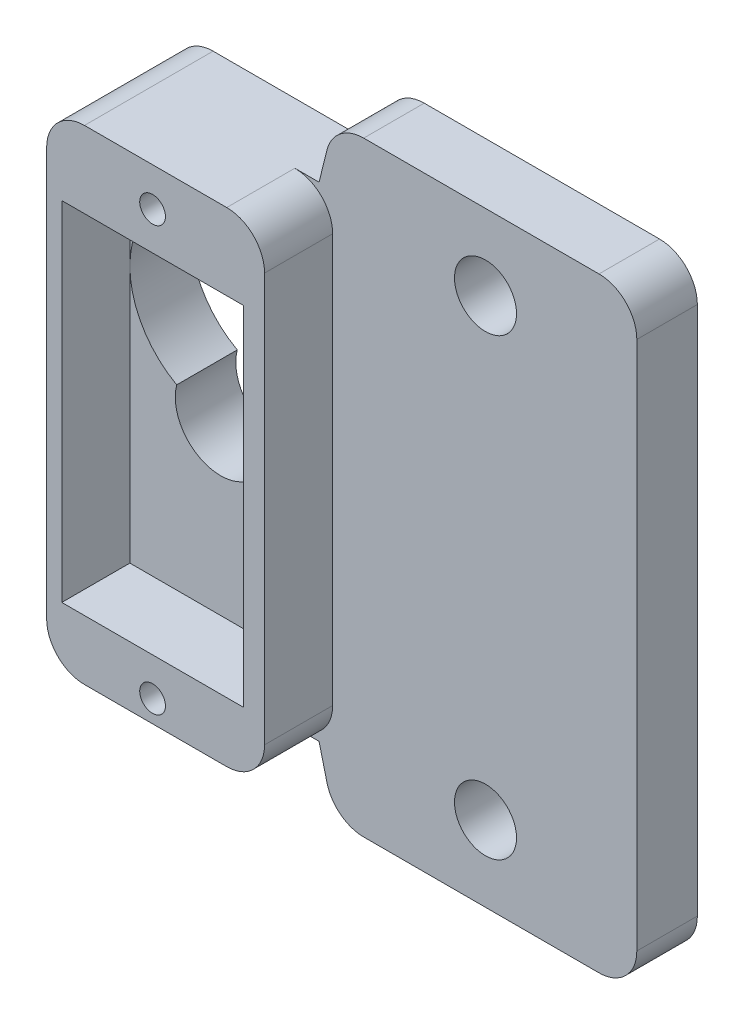
SolidWorks part; units mm, degrees
ref_plane "Plan de face" through (0, 0, 0) normal (0, 0, 1) x (1, 0, 0)
ref_plane "Plan de dessus" through (0, 0, 0) normal (0, 1, 0) x (1, 0, 0)
ref_plane "Plan de droite" through (0, 0, 0) normal (1, 0, 0) x (0, 0, -1)
sketch "Esquisse1" plane through (0, 0, 0) normal (0, 0, 1) x (1, 0, 0)
  line L0 (0, 19.6765) -> (0, -23.203) construction
  line L1 (-40.2718, 0) -> (44.7659, 0) construction
  line L2 (0, 20) -> (20, 20)
  line L3 (20, 20) -> (20, -20)
  line L4 (20, -20) -> (0, -20)
  line L5 (0, -20) -> (-14.5, -20) construction
  line L6 (-14.5, -20) -> (-14.5, 20) construction
  line L7 (-14.5, 20) -> (0, 20) construction
  line L8 (-7.5, 20) -> (-7.5, -20) construction
  line L9 (10, 20) -> (10, -20) construction
  line L10 (0, 20) -> (0, 16) construction
  line L11 (0, 16) -> (-14.5, 16) construction
  line L12 (-14.5, 16) -> (-14.5, -16)
  line L13 (0, -20) -> (0, -16) construction
  line L14 (0, -16) -> (-14.5, -16) construction
  line L15 (0, 20) -> (-1, 16)
  line L16 (-1, 16) -> (-14.5, 16)
  line L17 (-1, -16) -> (-14.5, -16)
  line L18 (0, -20) -> (-1, -16)
  circle A0 centre (-7.5, 4.95) radius 6 construction
  circle A1 centre (10, 15) radius 2.05
  circle A2 centre (10, -15) radius 2.05
  arc A3 (-10.4047, -0.3) -> (-4.5953, -0.3) centre (-7.5, -1.05) ccw construction
  arc A4 (-10.4047, -0.3) -> (-4.5953, -0.3) centre (-7.5, 4.95) cw
  arc A5 (-10.4047, -0.3) -> (-4.5953, -0.3) centre (-7.5, -1.05) ccw
  point P30 (-14.5, 0)
  dimension "D4" = 12
  dimension "D5" = 3
  dimension "D7" = 7
  dimension "D9" = 4.1
  dimension "D1" = 20
  dimension "D2" = 40
  dimension "D3" = 7.5
  dimension "D6" = 4.95
  dimension "D8" = 15
  dimension "D10" = 16
  dimension "D11" = 1
extrude "Boss.-Extru.1" add sketch "Esquisse1" along normal blind 4 contours L7 L6 L5 L4 L3 L2 A5 A4 A1 A2 region at (4.7951, -0.4724, 0)
sketch "Esquisse2" plane through (0, 0, 4) normal (0, 0, 1) x (1, 0, 0)
  line L0 (-7.5, 16.6119) -> (-7.5, -16.6119) construction
  line L1 (-0.1, 13.5) -> (-0.1, -13.5)
  line L2 (-1.5, -12.05) -> (-13.5, -12.05)
  line L3 (-1.5, -12.05) -> (-1.5, 10.95)
  line L4 (20, 20) -> (0, 20)
  line L5 (-1, -16) -> (0, -20)
  line L6 (0, -20) -> (20, -20)
  line L7 (20, -20) -> (20, 20)
  line L8 (20, 20) -> (0, 20)
  line L10 (0, -20) -> (20, -20)
  line L11 (20, -20) -> (20, 20)
  line L12 (-1.5, 10.95) -> (-13.5, 10.95)
  line L13 (-13.5, -12.05) -> (-13.5, 10.95)
  line L14 (-1.5, -12.05) -> (-13.5, 10.95) construction
  line L15 (-1.5, 10.95) -> (-13.5, -12.05) construction
  line L21 (-0.1, -16) -> (-1, -16)
  line L23 (-2.6, 16) -> (-14.5, 16)
  line L24 (-14.5, -16) -> (-2.6, -16)
  line L28 (-1, -16) -> (0, -20)
  line L30 (0, 20) -> (-1, 16)
  line L32 (0, 20) -> (-1, 16)
  line L34 (-1, 16) -> (-14.5, 16)
  line L36 (-14.5, 16) -> (-14.5, -16)
  line L37 (-14.5, 16) -> (-14.5, -16)
  line L38 (-1, 16) -> (-14.5, 16)
  line L39 (-14.5, -16) -> (-1, -16)
  line L40 (-14.5, -16) -> (-1, -16)
  arc A0 (-10.4047, -0.3) -> (-4.5953, -0.3) centre (-7.5, -1.05) ccw construction
  arc A1 (-4.5953, -0.3) -> (-10.4047, -0.3) centre (-7.5, 4.95) ccw construction
  arc A2 (-10.4047, -0.3) -> (-4.5953, -0.3) centre (-7.5, -1.05) ccw
  arc A3 (-4.5953, -0.3) -> (-10.4047, -0.3) centre (-7.5, 4.95) ccw
  arc A4 (-0.1, -13.5) -> (-2.6, -16) centre (-2.6, -13.5) cw
  arc A5 (-0.1, 13.5) -> (-2.6, 16) centre (-2.6, 13.5) ccw
  point P10 (-7.5, -0.55)
  point P15 (-7.5, -0.55)
  dimension "D4" = 2.5
  dimension "D5" = 2.5
  dimension "D2" = 23
  dimension "D3" = 1.4
  dimension "D1" = 0
extrude "Boss.-Extru.2" add sketch "Esquisse2" along normal blind 4.5 contours L2 L13 L12 L3 region at (-0.4509, 0, 4)
sketch "Esquisse3" plane through (0, 0, 8.5) normal (0, 0, 1) x (1, 0, 0)
  line L0 (-7.5, 37.9) -> (-7.5, -16) construction
  line L1 (-1.5, 10.95) -> (-7.5, 10.95) construction
  line L2 (-1.5, -12.05) -> (-13.5, -12.05) construction
  line L4 (-0.1, -13.5) -> (-0.1, 13.5)
  line L5 (-2.6, 16) -> (-14.5, 16)
  line L12 (-7.5, 10.95) -> (-13.5, 10.95) construction
  line L13 (-1.5, -12.05) -> (-13.5, -12.05) construction
  line L14 (-7.5, 10.95) -> (-13.5, 10.95)
  line L16 (-14.5, 16) -> (-14.5, -16)
  line L18 (-14.5, 16) -> (-14.5, -16)
  line L19 (-2.6, 16) -> (-14.5, 16)
  line L21 (-14.5, -16) -> (-2.6, -16)
  line L22 (-14.5, -16) -> (-2.6, -16)
  line L24 (-1.5, -12.05) -> (-13.5, -12.05)
  line L25 (-1.5, 10.95) -> (-7.5, 10.95)
  line L34 (-0.1, -13.5) -> (-0.1, 13.5)
  circle A0 centre (-7.5, 13.45) radius 0.85
  circle A1 centre (-7.5, -14.55) radius 0.85
  arc A2 (-0.1, -13.5) -> (-2.6, -16) centre (-2.6, -13.5) cw
  arc A3 (-0.1, 13.5) -> (-2.6, 16) centre (-2.6, 13.5) ccw
  arc A6 (-0.1, 13.5) -> (-2.6, 16) centre (-2.6, 13.5) ccw
  arc A7 (-0.1, 13.5) -> (-2.6, 16) centre (-2.6, 13.5) ccw
  arc A8 (-2.6, -16) -> (-0.1, -13.5) centre (-2.6, -13.5) ccw
  arc A9 (-2.6, -16) -> (-0.1, -13.5) centre (-2.6, -13.5) ccw
  dimension "D2" = 2.5
  dimension "D4" = 1.7
  dimension "D5" = 2.5
  dimension "D3" = 2.5
  dimension "D1" = 0
extrude "Enlèv. mat.-Extru.1" cut sketch "Esquisse3" against normal blind 8 contours A0 | A1
fillet "Congé1" radius 2.5 6 edges at (20, 20, 2) (20, -20, 2) (0, 20, 2) (0, -20, 2) (-14.5, -16, 4.25) (-14.5, 16, 4.25)
